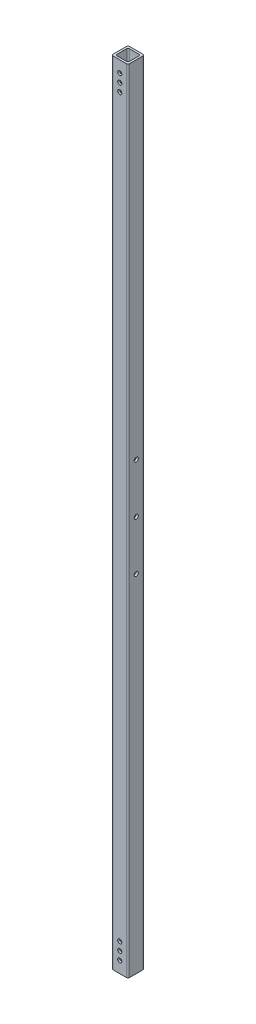
SolidWorks part; units mm, degrees
material "6061-T6 (SS)"
ref_plane "Front Plane" through (0, 0, 0) normal (0, 0, 1) x (1, 0, 0)
ref_plane "Top Plane" through (0, 0, 0) normal (0, 1, 0) x (1, 0, 0)
ref_plane "Right Plane" through (0, 0, 0) normal (1, 0, 0) x (0, 0, -1)
sketch "Sketch1" plane through (0, 0, 0) normal (0, 1, 0) x (1, 0, 0)
  line L0 (9.525, 9.525) -> (-9.525, 9.525)
  line L1 (12.7, -12.7) -> (-12.7, -12.7)
  line L2 (12.7, -12.7) -> (12.7, 12.7)
  line L3 (12.7, 12.7) -> (-12.7, 12.7)
  line L4 (-12.7, -12.7) -> (-12.7, 12.7)
  line L5 (12.7, -12.7) -> (-12.7, 12.7) construction
  line L6 (12.7, 12.7) -> (-12.7, -12.7) construction
  line L7 (-9.525, -9.525) -> (-9.525, 9.525)
  line L8 (9.525, -9.525) -> (-9.525, -9.525)
  line L9 (9.525, -9.525) -> (9.525, 9.525)
  point P0 (0, 0)
  dimension "D1" = 25.4
  dimension "D2" = 25.4
  dimension "D3" = 3.175
extrude "Boss-Extrude1" add sketch "Sketch1" along normal mid plane 1219.2
fillet "Fillet1" radius 2.1082 8 edges at (9.525, 0, -9.525) (-9.525, 0, -9.525) (-9.525, 0, 9.525) (9.525, 0, 9.525) (12.7, 0, -12.7) (-12.7, 0, -12.7) (-12.7, 0, 12.7) (12.7, 0, 12.7)
sketch "Sketch6" plane through (0, 0, -12.7) normal (0, 0, -1) x (-1, 0, 0)
  line L0 (0, 601.98) -> (0, 609.6) construction
  line L1 (0, 601.98) -> (0, 551.18) construction
  line L2 (0, 402.295) -> (0, -606.425) construction
  line L3 (-10.5918, 609.6) -> (10.5918, 609.6) construction
  line L4 (0, -609.6) -> (0, 601.98) construction
  line L5 (-10.5918, -609.6) -> (10.5918, -609.6) construction
  line L7 (0, 0) -> (10.5918, 0) construction
  line L8 (10.5918, -609.6) -> (10.5918, 609.6) construction
  circle A6 centre (0, 566.42) radius 3.175
  circle A7 centre (0, 579.12) radius 3.175
  circle A8 centre (0, 591.82) radius 3.175
  point P24 (0, 566.42)
  point P26 (0, 579.12)
  point P27 (0, 591.82)
  dimension "D9" = 6.35
  dimension "D2" = 7.62
  dimension "D6" = 15.24
  dimension "D7" = 12.7
  dimension "D8" = 12.7
  dimension "D10" = 50.8
extrude "Cut-Extrude5" cut sketch "Sketch6" against normal through all
sketch "Sketch7" plane through (-12.7, 0, 0) normal (-1, 0, 0) x (0, 0, 1)
  circle A0 centre (0, 0) radius 3.175
  dimension "D1" = 6.35
extrude "Cut-Extrude6" cut sketch "Sketch7" against normal through all
sketch "Sketch8" plane through (-12.7, 0, 0) normal (-1, 0, 0) x (0, 0, 1)
  line L0 (0, 0) -> (0, -76.2) construction
  circle A0 centre (0, -76.2) radius 3.175
  dimension "D2" = 6.35
  dimension "D1" = 76.2
extrude "Cut-Extrude7" cut sketch "Sketch8" against normal through all
mirror "Mirror1" about plane through (0, 0, 0) normal (0, 1, 0) of "Cut-Extrude7"
mirror "Mirror2" about plane through (0, 0, 0) normal (0, 1, 0) of face at (3.175, 566.42, -9.525) of face at (-3.175, 591.82, 9.525) of face at (-3.175, 579.12, 9.525) of face at (-3.175, 566.42, 9.525) of face at (3.175, 591.82, -9.525) of face at (3.175, 579.12, -9.525)
